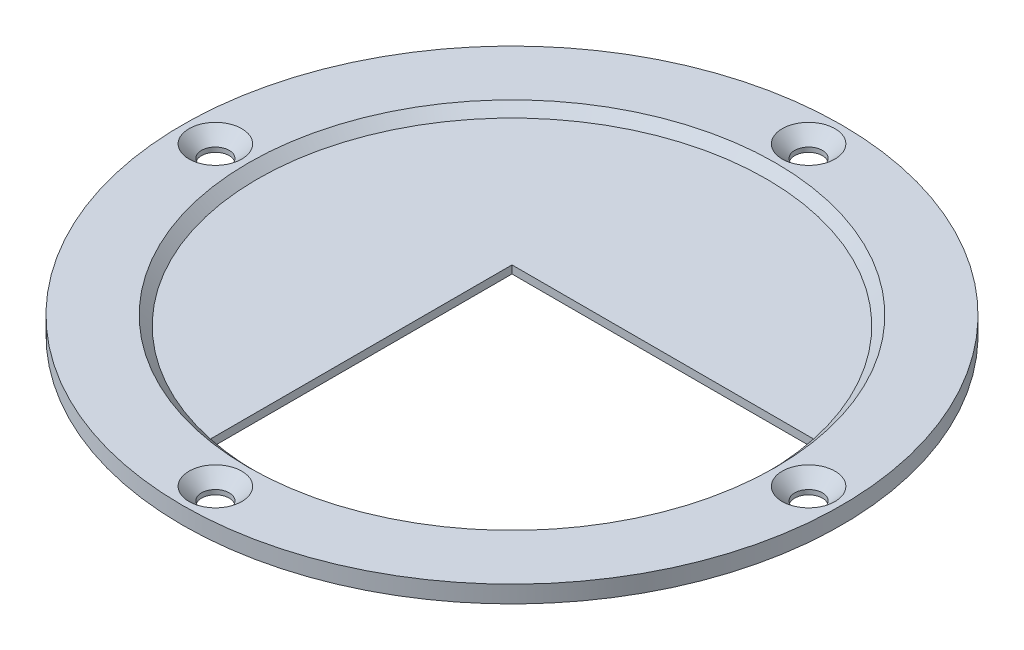
SolidWorks part; units mm, degrees
ref_plane "Front Plane" through (0, 0, 0) normal (0, 0, 1) x (1, 0, 0)
ref_plane "Top Plane" through (0, 0, 0) normal (0, 1, 0) x (1, 0, 0)
ref_plane "Right Plane" through (0, 0, 0) normal (1, 0, 0) x (0, 0, -1)
sketch "Sketch1" plane through (0, 0, 0) normal (0, 1, 0) x (1, 0, 0)
  line L0 (0, 0) -> (0, 45) construction
  line L1 (0, 0) -> (45, 0) construction
  line L8 (-8, 0) -> (-8, 8)
  line L9 (-8, 8) -> (37.7619, 8)
  line L10 (-8, 0) -> (-8, -37.7619)
  circle A0 centre (0, 0) radius 50
  circle A1 centre (45, 0) radius 2.1
  circle A2 centre (0, 45) radius 2.1
  circle A3 centre (0, -45) radius 2.1
  circle A4 centre (-45, 0) radius 2.1
  arc A6 (-8, -37.7619) -> (37.7619, 8) centre (0, 0) ccw
  circle A7 centre (0, 0) radius 8 construction
  circle A8 centre (0, 0) radius 38.6 construction
  dimension "D1" = 100
  dimension "D4" = 4.2
  dimension "D5" = 4.2
  dimension "D7" = 16
  dimension "D2" = 45
  dimension "D3" = 45
  dimension "D6" = 11.4
extrude "Boss-Extrude1" add sketch "Sketch1" along normal blind 1.2
sketch "Sketch2" plane through (0, 1.2, 0) normal (0, 1, 0) x (1, 0, 0)
  circle A0 centre (0, 0) radius 50 construction
  circle A1 centre (45, 0) radius 2.1
  circle A2 centre (45, 0) radius 2.1
  circle A3 centre (0, 45) radius 2.1
  circle A4 centre (0, 45) radius 2.1
  circle A5 centre (0, -45) radius 2.1
  circle A6 centre (0, -45) radius 2.1
  circle A7 centre (-45, 0) radius 2.1
  circle A8 centre (-45, 0) radius 2.1
  circle A9 centre (0, 0) radius 50
  circle A10 centre (0, 0) radius 40
  dimension "D1" = 0
  dimension "D2" = 0
  dimension "D3" = 0
  dimension "D4" = 0
  dimension "D5" = 10
extrude "Boss-Extrude2" add sketch "Sketch2" along normal blind 1.4
chamfer "Chamfer1" distance 1.4 angle 45 1 edges at (0, 1.2, 40)
chamfer "Chamfer2" distance 1.9 angle 45 4 edges at (0, 2.6, 47.1) (45, 2.6, 2.1) (0, 2.6, -42.9) (-45, 2.6, 2.1)
